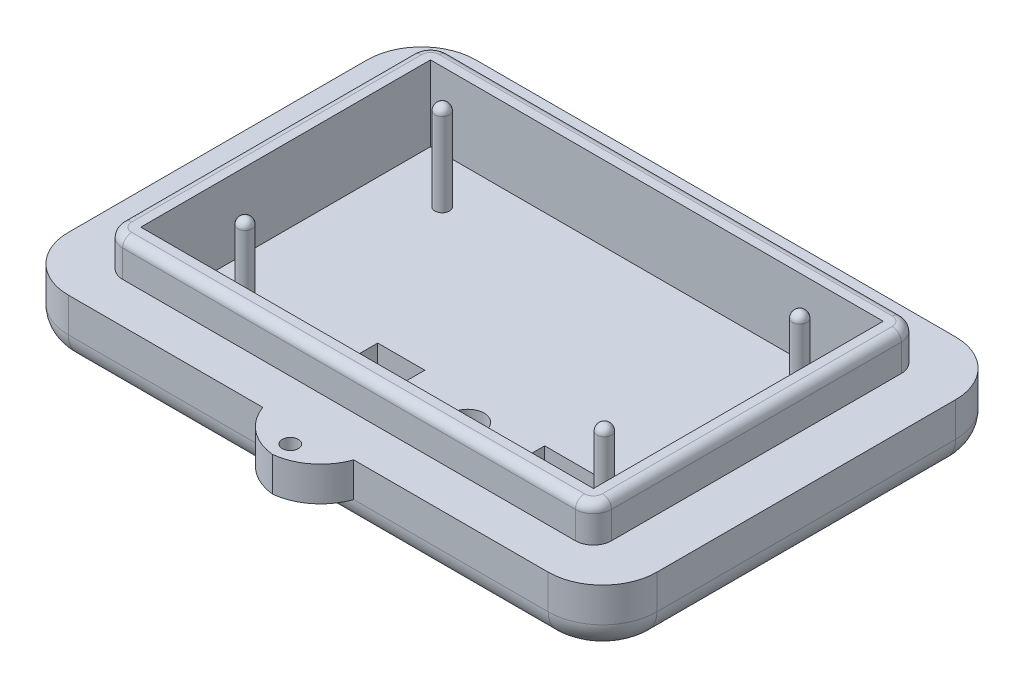
SolidWorks part; units mm, degrees
ref_plane "Front Plane" through (0, 0, 0) normal (0, 0, 1) x (1, 0, 0)
ref_plane "Top Plane" through (0, 0, 0) normal (0, 1, 0) x (1, 0, 0)
ref_plane "Right Plane" through (0, 0, 0) normal (1, 0, 0) x (0, 0, -1)
sketch "Sketch1" plane through (0, 0, 0) normal (0, 1, 0) x (1, 0, 0)
  line L1 (0, 0) -> (82.55, 0)
  line L2 (0, 0) -> (0, 57.15)
  line L3 (0, 57.15) -> (82.55, 57.15)
  line L4 (82.55, 0) -> (82.55, 57.15)
  dimension "D1" = 57.15
  dimension "D2" = 82.55
extrude "Boss-Extrude1" add sketch "Sketch1" along normal blind 8.636
fillet "Fillet2" radius 7.62 4 edges at (82.55, 4.318, -57.15) (82.55, 4.318, 0) (0, 4.318, 0) (0, 4.318, -57.15)
fillet "Fillet3" radius 3.81 8 edges at (80.3182, 0, -54.9182) (82.55, 0, -28.575) (80.3182, 0, -2.2318) (41.275, 0, 0) (2.2318, 0, -2.2318) (0, 0, -28.575) (2.2318, 0, -54.9182) (41.275, 0, -57.15)
sketch "Sketch2" plane through (0, 8.636, 0) normal (0, 1, 0) x (1, 0, 0)
  line L0 (0, 28.575) -> (82.55, 28.575) construction
  line L1 (0, 49.53) -> (0, 7.62) construction
  line L2 (82.55, 7.62) -> (82.55, 49.53) construction
  line L4 (9.525, 8.255) -> (73.025, 8.255)
  line L5 (9.525, 8.255) -> (9.525, 48.895)
  line L6 (9.525, 48.895) -> (73.025, 48.895)
  line L7 (73.025, 8.255) -> (73.025, 48.895)
  line L8 (9.525, 8.255) -> (73.025, 48.895) construction
  line L9 (9.525, 48.895) -> (73.025, 8.255) construction
  point P6 (41.275, 28.575)
  dimension "D1" = 40.64
  dimension "D2" = 63.5
extrude "Cut-Extrude1" cut sketch "Sketch2" against normal blind 5.461
sketch "Sketch7" plane through (0, 8.636, 0) normal (0, 1, 0) x (1, 0, 0)
  line L14 (6.985, 51.435) -> (6.985, 5.715)
  line L15 (6.985, 5.715) -> (75.565, 5.715)
  line L16 (75.565, 5.715) -> (75.565, 51.435)
  line L17 (75.565, 51.435) -> (6.985, 51.435)
  line L18 (6.985, 51.435) -> (6.985, 5.715)
  line L19 (6.985, 5.715) -> (75.565, 5.715)
  line L20 (75.565, 5.715) -> (75.565, 51.435)
  line L21 (75.565, 51.435) -> (6.985, 51.435)
  dimension "D1" = 2.54
extrude "Boss-Extrude3" add sketch "Sketch7" along normal blind 5.08
sketch "Sketch8" plane through (0, 13.716, 0) normal (0, 1, 0) x (1, 0, 0)
  line L8 (73.025, 48.895) -> (9.525, 48.895)
  line L9 (9.525, 48.895) -> (9.525, 8.255)
  line L10 (9.525, 8.255) -> (73.025, 8.255)
  line L11 (73.025, 8.255) -> (73.025, 48.895)
  line L12 (73.025, 48.895) -> (9.525, 48.895)
  line L13 (9.525, 48.895) -> (9.525, 8.255)
  line L14 (9.525, 8.255) -> (73.025, 8.255)
  line L15 (73.025, 8.255) -> (73.025, 48.895)
  dimension "D1" = 2.54
extrude "Cut-Extrude3" cut sketch "Sketch8" against normal blind 5.08
sketch "Sketch5" plane through (0, 3.175, 0) normal (0, 1, 0) x (1, 0, 0)
  line L3 (9.525, 8.255) -> (73.025, 8.255) construction
  line L4 (73.025, 8.255) -> (73.025, 48.895) construction
  circle A0 centre (17.665, 42.392) radius 1.016
  circle A1 centre (17.665, 14.732) radius 1.016
  circle A2 centre (67.945, 42.259) radius 1.016
  circle A3 centre (67.945, 14.859) radius 1.016
  point P2 (0, 0)
  point P3 (0, 0)
  dimension "D5" = 2.032
  dimension "D6" = 2.032
  dimension "D7" = 2.032
  dimension "D8" = 2.032
  dimension "D11" = 6.604
  dimension "D2" = 27.66
  dimension "D3" = 6.477
  dimension "D4" = 50.28
  dimension "D9" = 27.4
  dimension "D10" = 5.08
  dimension "D12" = 5.08
  dimension "D13" = 50.28
extrude "Boss-Extrude4" add sketch "Sketch5" along normal blind 12.7
sketch "Sketch4" plane through (0, 3.175, 0) normal (0, 1, 0) x (1, 0, 0)
  line L4 (66.471, 20.559) -> (53.871, 20.559)
  line L5 (66.471, 20.559) -> (66.471, 15.559)
  line L6 (66.471, 15.559) -> (53.871, 15.559)
  line L7 (53.871, 20.559) -> (53.871, 15.559)
  line L8 (66.471, 20.559) -> (53.871, 15.559) construction
  line L9 (66.471, 15.559) -> (53.871, 20.559) construction
  line L11 (36.285, 21.336) -> (29.681, 21.336)
  line L12 (36.285, 21.336) -> (36.285, 14.732)
  line L13 (36.285, 14.732) -> (29.681, 14.732)
  line L14 (29.681, 21.336) -> (29.681, 14.732)
  line L15 (36.285, 21.336) -> (29.681, 14.732) construction
  line L16 (36.285, 14.732) -> (29.681, 21.336) construction
  circle A0 centre (45.641, 18.034) radius 2.25
  circle A1 centre (17.665, 14.732) radius 1.016 construction
  circle A2 centre (67.945, 14.859) radius 1.016 construction
  point P7 (60.171, 18.059)
  point P15 (32.983, 18.034)
  dimension "D3" = 4.5
  dimension "D4" = 5.7
  dimension "D2" = 15.96
  dimension "D5" = 12.6
  dimension "D6" = 5
  dimension "D7" = 20.83
  dimension "D8" = 6.604
  dimension "D9" = 6.604
  dimension "D10" = 0
  dimension "D11" = 18.62
  dimension "D13" = 0
extrude "Cut-Extrude2" cut sketch "Sketch4" against normal blind 7.366
fillet "Fillet7" radius 1.016 3 edges at (17.665, 15.875, -13.716) (17.665, 15.875, -41.376) (67.945, 15.875, -41.243)
fillet "Fillet8" radius 2.54 4 edges at (75.565, 11.176, -51.435) (75.565, 11.176, -5.715) (6.985, 11.176, -5.715) (6.985, 11.176, -51.435)
sketch "Sketch9" plane through (0, 0, 0) normal (0, 0, 1) x (1, 0, 0)
  line L0 (41.275, 8.636) -> (41.275, 3.81) construction
  line L1 (7.62, 8.636) -> (74.93, 8.636) construction
  line L2 (7.62, 3.81) -> (74.93, 3.81) construction
  line L4 (47.6519, 8.636) -> (34.8981, 8.636)
  line L5 (47.6519, 8.636) -> (47.6519, 3.81)
  line L6 (47.6519, 3.81) -> (34.8981, 3.81)
  line L7 (34.8981, 8.636) -> (34.8981, 3.81)
  line L8 (47.6519, 8.636) -> (34.8981, 3.81) construction
  line L9 (47.6519, 3.81) -> (34.8981, 8.636) construction
  point P6 (41.275, 6.223)
extrude "Boss-Extrude5" add sketch "Sketch9" along normal blind 5.08
fillet "Fillet10" radius 7.62 2 edges at (47.6519, 6.223, 5.08) (34.8981, 6.223, 5.08)
fillet "Fillet11" radius 1.27 8 edges at (74.8211, 13.716, -50.6911) (75.565, 13.716, -28.575) (74.8211, 13.716, -6.4589) (41.275, 13.716, -5.715) (7.7289, 13.716, -6.4589) (7.7289, 13.716, -50.6911) (6.985, 13.716, -28.575) (41.275, 13.716, -51.435)
fillet "Fillet12" radius 1.016 1 edges at (67.945, 15.875, -13.843)
sketch "Sketch17" plane through (0, 3.81, 0) normal (0, -1, 0) x (1, 0, 0)
  line L0 (41.275, 5.0371) -> (41.275, 0) construction
  point P3 (41.275, 2.5186)
hole_wizard "#4-40 Tapped Hole2" positions "Sketch18" profile "Sketch19" tap size "#4-40" standard "ANSI Inch"
sketch "Sketch18" plane through (0, 3.81, 0) normal (0, -1, 0) x (-1, 0, 0)
  point P0 (-41.275, -2.5186)
sketch "Sketch19" plane through (41.275, 3.81, 2.5186) normal (1, 0, 0) x (0, 0, -1)
  line L0 (0, 0) -> (0, 8.2992)
  line L1 (0, 8.2992) -> (1.1303, 7.62)
  line L2 (1.1303, 7.62) -> (1.1303, 0.7779)
  line L3 (1.1303, 0.7779) -> (2.0574, 0)
  line L5 (2.0574, 0) -> (0, 0)
  line L6 (-1.1303, 0.7779) -> (-2.0574, 0) construction
  line L10 (0, 8.2992) -> (-1.1303, 7.62) construction
  line L11 (0, -6.35) -> (0, 107.95) construction
  dimension "Tap Drill Dia." = 2.2606
  dimension "Tap Drill Depth" = 7.62
  dimension "Near C'Sink Dia." = 4.1148
  dimension "Near C'Sink Angle" = 100
  dimension "Drill Angle" = 118
cosmetic thread "Hole Thread2" parameters "D1"=4.826, "D2"=2.8448
